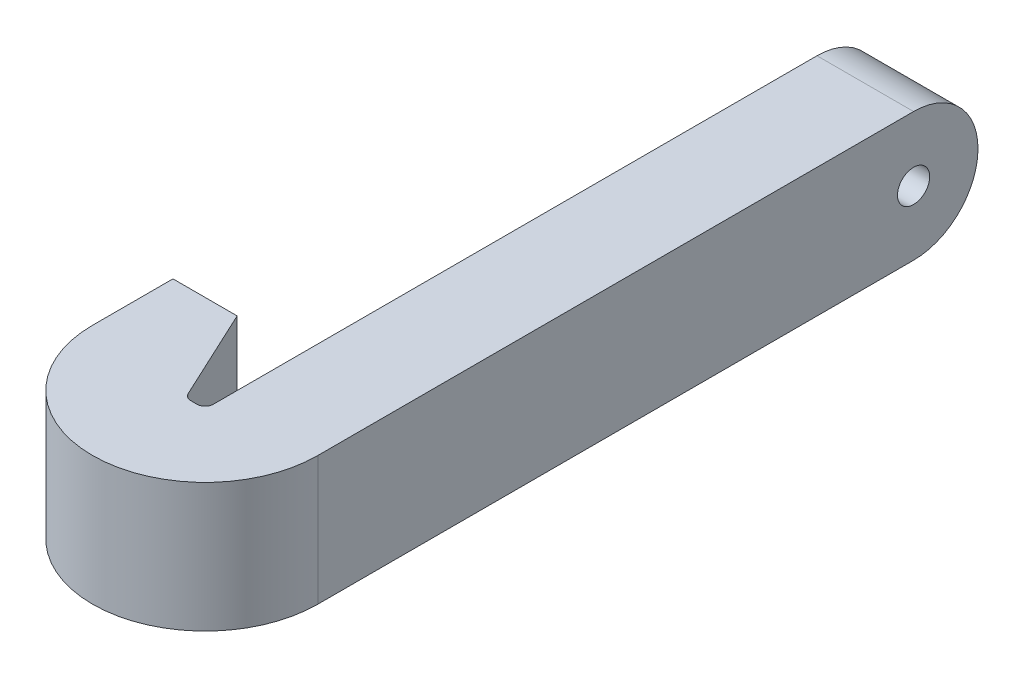
SolidWorks part; units mm, degrees
material "Polycarbonate"
ref_plane "Front Plane" through (0, 0, 0) normal (0, 0, 1) x (1, 0, 0)
ref_plane "Top Plane" through (0, 0, 0) normal (0, 1, 0) x (1, 0, 0)
ref_plane "Right Plane" through (0, 0, 0) normal (1, 0, 0) x (0, 0, -1)
sketch "Sketch1" plane through (0, 0, 0) normal (0, 1, 0) x (1, 0, 0)
  line L0 (0, 0) -> (-7.9375, 0)
  line L13 (0, 0) -> (3.175, 0)
  line L14 (-1.5875, 4.7625) -> (-1.5875, 38.1)
  line L15 (-1.5875, 38.1) -> (3.175, 38.1)
  line L16 (3.175, 0) -> (3.175, 38.1)
  line L17 (-7.9375, 0) -> (-7.9375, 9.525)
  line L18 (-7.9375, 9.525) -> (-4.7735, 9.525)
  line L19 (-4.7735, 9.525) -> (-2.5527, 4.7625)
  line L20 (-2.5527, 4.7625) -> (-1.5875, 4.7625)
  dimension "D1" = 4.7625
  dimension "D2" = 6.35
  dimension "D3" = 9.525
  dimension "D4" = 25
  dimension "D5" = 4.7625
  dimension "D6" = 0.9652
  dimension "D8" = 38.1
extrude "Boss-Extrude1" add sketch "Sketch1" along normal blind 6.35
fillet "Fillet1" radius 0.3969 2 edges at (-2.5527, 3.175, -4.7625) (-1.5875, 3.175, -4.7625)
fillet "Fillet3" 2 edges at (-7.9375, 3.175, 0) (3.175, 3.175, 0) type full round first side face at (-7.9375, 3.175, -4.7625) second side face at (3.175, 3.175, -19.05) middle face at (-2.3812, 3.175, 0)
fillet "Fillet4" 2 edges at (0.7938, 0, -38.1) (0.7938, 6.35, -38.1) type full round first side face at (-2.4368, 0, -12.0348) second side face at (-2.4368, 6.35, -12.0348) middle face at (0.7938, 3.175, -38.1)
sketch "Sketch2" plane through (3.175, 0, 0) normal (1, 0, 0) x (0, 0, -1)
  circle A0 centre (34.925, 3.175) radius 0.7937
  arc A1 (34.925, 0) -> (34.925, 6.35) centre (34.925, 3.175) ccw construction
  dimension "D1" = 1.5875
extrude "Cut-Extrude1" cut sketch "Sketch2" against normal through all
